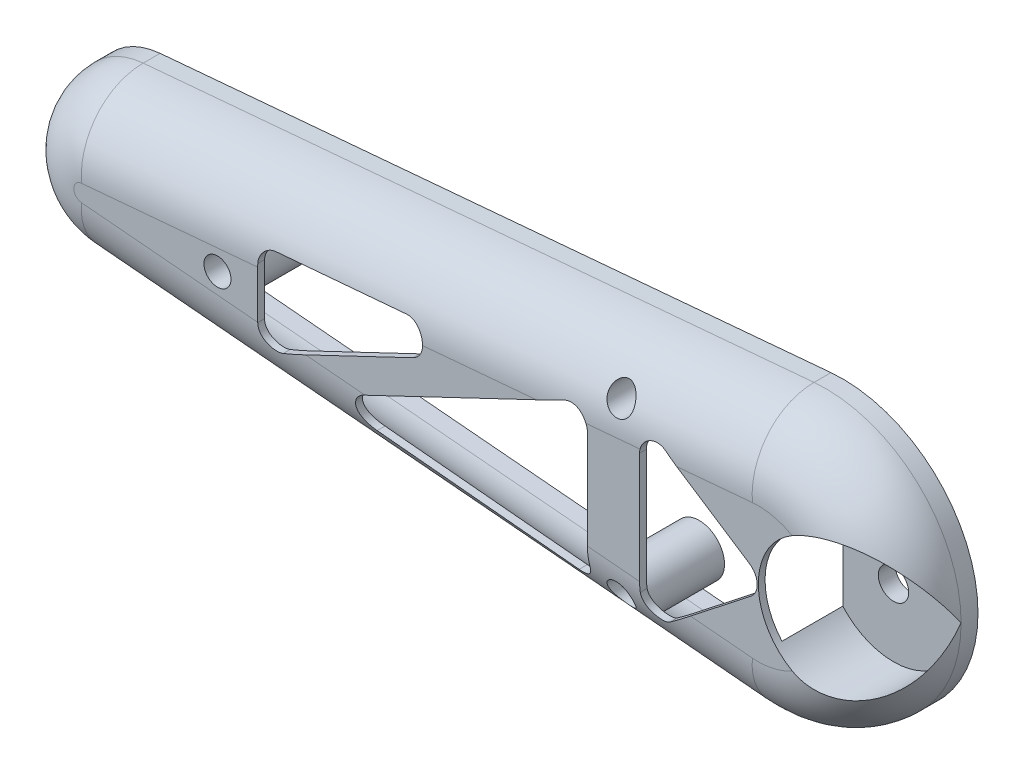
SolidWorks part; units mm, degrees
ref_plane "Front Plane" through (0, 0, 0) normal (0, 0, 1) x (1, 0, 0)
ref_plane "Top Plane" through (0, 0, 0) normal (0, 1, 0) x (1, 0, 0)
ref_plane "Right Plane" through (0, 0, 0) normal (1, 0, 0) x (0, 0, -1)
sketch "Sketch1" plane through (0, 0, 0) normal (0, 0, 1) x (1, 0, 0)
  line L0 (-100, 0) -> (100, 0) construction
  line L1 (-101.9688, 22.4137) -> (96.5, 39.8466)
  line L4 (96.5, -39.8466) -> (-101.9688, -22.4137)
  arc A0 (96.5, -39.8466) -> (96.5, 39.8466) centre (100, 0) ccw
  arc A1 (-101.9688, 22.4137) -> (-101.9688, -22.4137) centre (-100, 0) ccw
  dimension "D2" = 80
  dimension "D3" = 45
  dimension "D1" = 200
extrude "Boss-Extrude1" add sketch "Sketch1" along normal blind 25 and the other way blind 25
fillet "Fillet1" radius 20 8 edges at (-2.7344, -31.1301, -25) (140, 0, -25) (-2.7344, 31.1301, -25) (-122.5, 0, -25) (-2.7344, 31.1301, 25) (140, 0, 25) (-2.7344, -31.1301, 25) (-122.5, 0, 25)
shell "Shell1" thickness 2
sketch "Sketch2" plane through (0, 0, 25) normal (0, 0, 1) x (1, 0, 0)
  line L0 (72.6238, 20.082) -> (97.4271, 3.8149)
  line L1 (97.7741, -4.2977) -> (72.9708, -23.786)
  line L2 (64.8817, -19.8544) -> (64.8817, 15.901)
  line L3 (49.4372, 13.583) -> (49.4372, -20.9242)
  line L4 (43.9049, -25.8958) -> (-15.1993, -19.5675)
  line L5 (-16.8188, -10.0826) -> (42.2854, 18.0963)
  line L6 (-2.1805, 6.8207) -> (-40.9454, -11.6611)
  line L7 (-48.0972, -7.1478) -> (-48.0972, 7.9923)
  line L8 (-43.5266, 12.9738) -> (-4.7617, 16.3156)
  arc A0 (97.4271, 3.8149) -> (97.7741, -4.2977) centre (94.685, -0.3661) cw
  arc A1 (72.6238, 20.082) -> (64.8817, 15.901) centre (69.8817, 15.901) ccw
  arc A2 (72.9708, -23.786) -> (64.8817, -19.8544) centre (69.8817, -19.8544) cw
  arc A3 (49.4372, -20.9242) -> (43.9049, -25.8958) centre (44.4372, -20.9242) cw
  arc A4 (49.4372, 13.583) -> (42.2854, 18.0963) centre (44.4372, 13.583) ccw
  arc A5 (-15.1993, -19.5675) -> (-16.8188, -10.0826) centre (-14.667, -14.5959) cw
  arc A6 (-2.1805, 6.8207) -> (-4.7617, 16.3156) centre (-4.3323, 11.334) ccw
  arc A7 (-48.0972, 7.9923) -> (-43.5266, 12.9738) centre (-43.0972, 7.9923) cw
  arc A8 (-40.9454, -11.6611) -> (-48.0972, -7.1478) centre (-43.0972, -7.1478) cw
  dimension "D1" = 5
extrude "Cut-Extrude1" cut sketch "Sketch2" against normal through all
sketch "Sketch4" plane through (0, 0, 0) normal (0, 0, 1) x (1, 0, 0)
  line L0 (-60, 0) -> (57.5, 0) construction
  line L1 (57.5, 25) -> (57.5, -25) construction
  circle A0 centre (-60, 0) radius 7.5
  circle A1 centre (57.5, 25) radius 7.5
  circle A2 centre (57.5, -25) radius 7.5
  point P6 (0, 0)
  dimension "D1" = 15
  dimension "D2" = 50
  dimension "D3" = 60
  dimension "D4" = 57.5
extrude "Boss-Extrude2" add sketch "Sketch4" along normal up to next and the other way up to next
sketch "Sketch5" plane through (0, 0, 0) normal (0, 0, 1) x (1, 0, 0)
  circle A0 centre (57.5, 25) radius 1.75
  circle A1 centre (57.5, -25) radius 1.75
  circle A2 centre (-60, 0) radius 1.75
  dimension "D1" = 3.5
extrude "Cut-Extrude2" cut sketch "Sketch5" against normal through all both and the other way through all
sketch "Sketch6" plane through (0, 0, 25) normal (0, 0, 1) x (1, 0, 0)
  circle A0 centre (57.5, 25) radius 4
  circle A1 centre (57.5, -25) radius 4
  circle A2 centre (-60, 0) radius 4
  dimension "D1" = 8
extrude "Cut-Extrude3" cut sketch "Sketch6" against normal blind 12
mirror "Mirror1" about plane through (0, 0, 0) normal (0, 0, 1) of "Cut-Extrude3"
chamfer "Chamfer1" distance 2 angle 45 6 edges at (61.5, -25, 13) (61.5, 25, 13) (-56, 0, 13) (-56, 0, -13) (61.5, -25, -13) (61.5, 25, -13)
sketch "Sketch7" plane through (0, 0, 0) normal (0, 0, 1) x (1, 0, 0)
  line L1 (-171.6611, 90.4785) -> (189.7069, 90.4785)
  line L2 (-171.6611, 90.4785) -> (-171.6611, -100.8501)
  line L3 (-171.6611, -100.8501) -> (189.7069, -100.8501)
  line L4 (189.7069, 90.4785) -> (189.7069, -100.8501)
extrude "Cut-Extrude4" cut sketch "Sketch7" against normal through all
sketch "Sketch8" plane through (0, 0, 0) normal (0, 0, -1) x (-1, 0, 0)
  line L0 (-105, 37.6696) -> (-105, -37.6696)
  arc A0 (-96.675, 37.8543) -> (-96.675, -37.8543) centre (-100, 0) ccw construction
  arc A1 (-105, 37.6696) -> (-105, -37.6696) centre (-100, 0) ccw
  point P1 (-110.3351, -36.5676)
  point P5 (-110.3864, 36.553)
  dimension "D1" = 5
extrude "Boss-Extrude3" add sketch "Sketch8" against normal up to next
sketch "Sketch9" plane through (0, 0, 25) normal (0, 0, 1) x (1, 0, 0)
  line L0 (120, 0) -> (0, 0) construction
  circle A0 centre (120, 0) radius 20
  dimension "D1" = 40
  dimension "D2" = 120
extrude "Cut-Extrude5" cut sketch "Sketch9" against normal blind 20
sketch "Sketch10" plane through (0, 0, 5) normal (0, 0, 1) x (1, 0, 0)
  circle A0 centre (120, 0) radius 4.5
  dimension "D1" = 9
extrude "Cut-Extrude6" cut sketch "Sketch10" against normal through all
